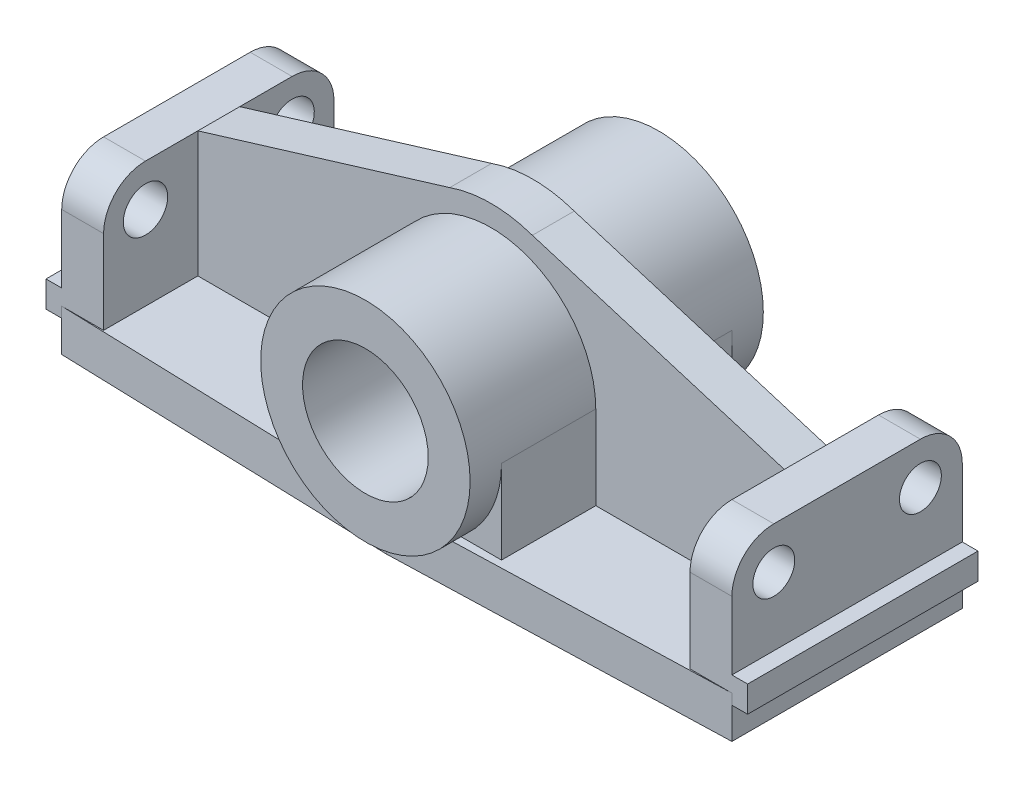
SolidWorks part; units mm, degrees
ref_plane "Front Plane" through (0, 0, 0) normal (0, 0, 1) x (1, 0, 0)
ref_plane "Top Plane" through (0, 0, 0) normal (0, 1, 0) x (1, 0, 0)
ref_plane "Right Plane" through (0, 0, 0) normal (1, 0, 0) x (0, 0, -1)
sketch "Sketch2" plane through (0, 0, 0) normal (0, 0, 1) x (1, 0, 0)
  line L0 (0, 0) -> (0, 76.2) construction
  line L1 (-88.9, 0) -> (88.9, 0)
  line L2 (88.9, 0) -> (88.9, 50.8)
  line L3 (88.9, 50.8) -> (12.523, 74.0831)
  line L4 (-88.9, 50.8) -> (-12.523, 74.0831)
  line L5 (-88.9, 0) -> (-88.9, 50.8)
  circle A0 centre (0, 38.1) radius 38.1
  circle A1 centre (0, 38.1) radius 31.75
  circle A2 centre (0, 38.1) radius 19.05
  dimension "D2" = 76.2
  dimension "D7" = 63.5
  dimension "D8" = 38.1
  dimension "D1" = 76.2
  dimension "D3" = 38.1
  dimension "D4" = 88.9
  dimension "D5" = 50.8
  dimension "D6" = 12.523
extrude "Boss-Extrude4" add sketch "Sketch2" along normal blind 6.35 contours L0 A0 A1 | A0 L1 L2 L3 | A0 L4 L5 L1 | A0 L0 A1 region at (-36.727, 31.8917, 0) region at (58.1033, 28.9544, 0) region at (-58.1033, 28.9544, 0) region at (0.8519, 3.175, 0)
sketch "Sketch4" plane through (0, 0, 0) normal (0, 0, -1) x (-1, 0, 0)
  line L0 (-88.9, 50.8) -> (-101.6, 50.8)
  line L1 (-101.6, 50.8) -> (-101.6, 0)
  line L2 (-101.6, 0) -> (101.6, 0)
  line L3 (88.9, 0) -> (-88.9, 0) construction
  line L4 (0, 0) -> (0, 76.2) construction
  line L5 (-88.9, 0) -> (-88.9, 50.8) construction
  line L6 (-88.9, 12.7) -> (-31.75, 12.7)
  line L7 (-31.75, 38.1) -> (-31.75, 12.7)
  line L8 (88.9, 12.7) -> (31.75, 12.7)
  line L9 (101.6, 50.8) -> (101.6, 0)
  line L10 (88.9, 50.8) -> (101.6, 50.8)
  line L11 (31.75, 38.1) -> (31.75, 12.7)
  arc A0 (12.523, 74.0831) -> (-12.523, 74.0831) centre (0, 38.1) ccw construction
  circle A1 centre (0, 38.1) radius 19.05
  arc A3 (31.75, 38.1) -> (-31.75, 38.1) centre (0, 38.1) ccw
  point P13 (-88.9, 12.7)
  circle M3 centre (0, 38.1) radius 31.75
  line M6 (-88.9, 50.8) -> (-88.9, 0)
  line M7 (-88.9, 0) -> (88.9, 0)
  line M8 (88.9, 0) -> (88.9, 50.8)
  dimension "D1" = 38.1
  dimension "D2" = 12.7
  dimension "D3" = 38.1
  dimension "D4" = 31.75
  dimension "D5" = 57.15
extrude "Boss-Extrude5" add sketch "Sketch4" against normal blind 34.925 contours L1 L2 L0 M6 | L6 M7 M3 M6 | L4 A1 M3 | L4 A3 A1 M3 | L8 L2 M8 M3 | L10 L2 L9 M8 region at (95.25, 25.4, 0) region at (45.7435, 7.1317, 0) region at (21.9486, 60.0486, 0) region at (-45.7435, 7.1317, 0) region at (-21.9486, 60.0486, 0) region at (-95.25, 25.4, 0)
sketch "Sketch5" plane through (101.6, 0, 0) normal (1, 0, 0) x (0, 0, -1)
  line L0 (0, 50.8) -> (0, 0) construction
  line L1 (-34.925, 50.8) -> (0, 50.8) construction
  circle A0 centre (-22.225, 38.1) radius 6.35
  dimension "D2" = 12.7
  dimension "D1" = 22.225
  dimension "D3" = 12.7
extrude "Cut-Extrude1" cut sketch "Sketch5" against normal up to surface (12.7 mm away) up to face at (88.9, 31.75, 20.6375)
sketch "Sketch6" plane through (-101.6, 0, 0) normal (-1, 0, 0) x (0, 0, 1)
  line L0 (0, 50.8) -> (0, 0) construction
  line L1 (34.925, 50.8) -> (0, 50.8) construction
  circle A0 centre (22.225, 38.1) radius 6.731
  dimension "D1" = 13.462
  dimension "D2" = 22.225
  dimension "D3" = 12.7
extrude "Cut-Extrude2" cut sketch "Sketch6" against normal up to surface (12.7 mm away) up to face at (-88.9, 31.75, 20.6375)
sketch "Sketch8" plane through (101.6, 0, 0) normal (1, 0, 0) x (0, 0, -1)
  line L0 (-34.925, 50.8) -> (-34.925, 0) construction
  line L1 (-34.925, 17.4625) -> (0, 17.4625)
  line L2 (-34.925, 17.4625) -> (-34.925, 9.525)
  line L3 (-34.925, 9.525) -> (0, 9.525)
  line L4 (0, 17.4625) -> (0, 9.525)
  line L5 (0, 50.8) -> (0, 0) construction
  line L6 (-34.925, 0) -> (0, 0) construction
  dimension "D1" = 7.9375
  dimension "D2" = 9.525
extrude "Boss-Extrude6" add sketch "Sketch8" along normal blind 4.7625
sketch "Sketch9" plane through (-101.6, 0, 0) normal (-1, 0, 0) x (0, 0, 1)
  line L0 (0, 50.8) -> (0, 0) construction
  line L1 (0, 17.4625) -> (34.925, 17.4625)
  line L2 (0, 17.4625) -> (0, 9.525)
  line L3 (0, 9.525) -> (34.925, 9.525)
  line L4 (34.925, 17.4625) -> (34.925, 9.525)
  line L5 (34.925, 50.8) -> (34.925, 0) construction
  line L6 (34.925, 0) -> (0, 0) construction
  dimension "D1" = 7.9375
  dimension "D2" = 9.525
extrude "Boss-Extrude7" add sketch "Sketch9" along normal blind 4.7625
fillet "Fillet1" radius 12.7 2 edges at (95.25, 50.8, 34.925) (-95.25, 50.8, 34.925)
mirror "Mirror1" about plane through (0, 0, 0) normal (0, 0, 1) of "Boss-Extrude4", "Boss-Extrude5", "Cut-Extrude1", "Cut-Extrude2", "Boss-Extrude6", "Boss-Extrude7", "Fillet1"
sketch "Sketch10" plane through (0, 0, 0) normal (0, 0, 1) x (1, 0, 0)
  circle A0 centre (0, 38.1) radius 31.75
  circle A1 centre (0, 38.1) radius 19.05
  dimension "D1" = 63.5
  dimension "D2" = 38.1
extrude "Boss-Extrude8" add sketch "Sketch10" along normal mid plane 88.9
sketch "Sketch11" plane through (0, 0, 0) normal (0, -1, 0) x (1, 0, 0)
  line L0 (0, 38.1) -> (0, -39.3843) construction
  line L1 (31.75, 34.925) -> (-31.75, 34.925) construction
  line L2 (0, 38.1) -> (101.6, 34.925)
  line L3 (101.6, 34.925) -> (-101.6, 34.925)
  line L4 (0, 34.925) -> (0, 38.1)
  line L5 (-106.3625, 0) -> (106.3625, 0) construction
  line L6 (-106.3625, -34.925) -> (-106.3625, 34.925) construction
  line L7 (106.3625, 34.925) -> (106.3625, -34.925) construction
  line L8 (0, 38.1) -> (-101.6, 34.925)
  line L9 (0, -38.1) -> (-101.6, -34.925)
  line L10 (0, -34.925) -> (0, -38.1)
  line L11 (101.6, -34.925) -> (-101.6, -34.925)
  line L12 (0, -38.1) -> (101.6, -34.925)
  line M4 (-101.6, -34.925) -> (101.6, -34.925)
  line M6 (101.6, 34.925) -> (-101.6, 34.925)
  dimension "D1" = 3.175
extrude "Boss-Extrude9" add sketch "Sketch11" against normal blind 12.7 contours L4 L8 L3 | L4 L2 M6 | L10 L12 M4 | L9 L11 L12 region at (33.8667, 0, 35.9833) region at (-33.8667, 0, 35.9833) region at (33.8667, 0, -35.9833)
